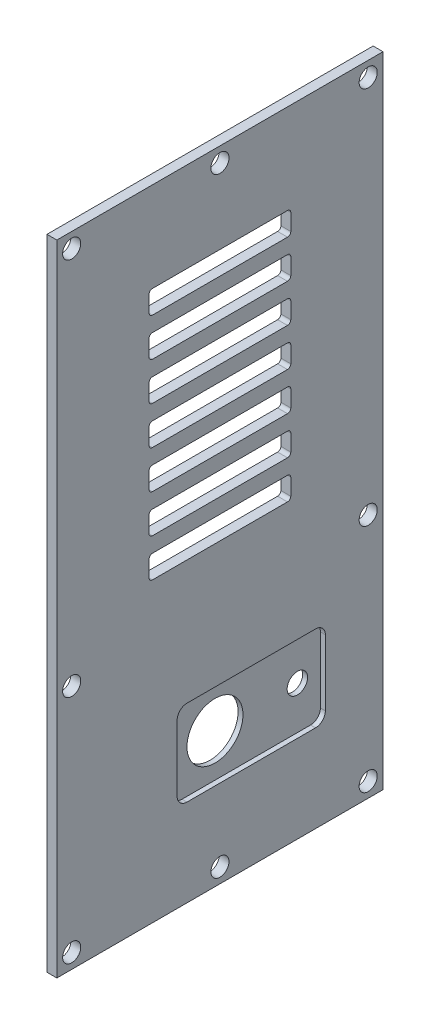
SolidWorks part; units mm, degrees
ref_plane "Front Plane" through (0, 0, 0) normal (0, 0, 1) x (1, 0, 0)
ref_plane "Top Plane" through (0, 0, 0) normal (0, 1, 0) x (1, 0, 0)
ref_plane "Right Plane" through (0, 0, 0) normal (1, 0, 0) x (0, 0, -1)
sketch "Sketch1" plane through (-74.9883, 0, 0) normal (-1, 0, 0) x (0, 0, 1)
  line L0 (-65.7307, 104.5) -> (-65.7307, -89.5)
  line L1 (-66.2307, 105) -> (33.7693, 105) construction
  line L2 (-66.2307, 105) -> (-66.2307, -90) construction
  line L3 (-66.2307, -90) -> (33.7693, -90) construction
  line L4 (33.7693, 105) -> (33.7693, -90) construction
  line L5 (-65.7307, -89.5) -> (33.2693, -89.5)
  line L6 (33.2693, 104.5) -> (33.2693, -89.5)
  line L7 (-65.7307, 104.5) -> (33.2693, 104.5)
  dimension "D1" = 0.5
extrude "Boss-Extrude1" add sketch "Sketch1" along normal blind 3
sketch "Sketch2" plane through (-77.9883, 0, 0) normal (-1, 0, 0) x (0, 0, 1)
  line L0 (-65.7307, 73.75) -> (33.2693, 73.75) construction
  line L1 (-65.7307, 104.5) -> (-65.7307, -89.5) construction
  line L2 (33.2693, -89.5) -> (33.2693, 104.5) construction
  line L3 (-16.2307, 104.5) -> (-16.2307, -89.5) construction
  line L4 (33.2693, 104.5) -> (-65.7307, 104.5) construction
  line L5 (-65.7307, -89.5) -> (33.2693, -89.5) construction
  line L6 (-65.7307, 62.15) -> (33.2693, 62.15) construction
  line L7 (33.2693, 50.55) -> (-65.7307, 50.55) construction
  line L8 (33.2693, 38.95) -> (-65.7307, 38.95) construction
  line L9 (-65.7307, 27.35) -> (33.2693, 27.35) construction
  line L10 (33.2693, 15.75) -> (-65.7307, 15.75) construction
  line L11 (33.2693, 4.15) -> (-65.7307, 4.15) construction
  line L13 (-37.7307, 70.25) -> (5.2693, 70.25)
  line L14 (-37.7307, 70.25) -> (-37.7307, 77.25)
  line L15 (-37.7307, 77.25) -> (5.2693, 77.25)
  line L16 (5.2693, 70.25) -> (5.2693, 77.25)
  line L17 (-37.7307, 70.25) -> (5.2693, 77.25) construction
  line L18 (-37.7307, 77.25) -> (5.2693, 70.25) construction
  line L19 (-37.7307, 58.65) -> (5.2693, 58.65)
  line L20 (-37.7307, 58.65) -> (-37.7307, 65.65)
  line L21 (-37.7307, 65.65) -> (5.2693, 65.65)
  line L22 (5.2693, 58.65) -> (5.2693, 65.65)
  line L23 (-37.7307, 58.65) -> (5.2693, 65.65) construction
  line L24 (-37.7307, 65.65) -> (5.2693, 58.65) construction
  line L25 (-37.7307, 47.05) -> (5.2693, 47.05)
  line L26 (-37.7307, 47.05) -> (-37.7307, 54.05)
  line L27 (-37.7307, 54.05) -> (5.2693, 54.05)
  line L28 (5.2693, 47.05) -> (5.2693, 54.05)
  line L29 (-37.7307, 47.05) -> (5.2693, 54.05) construction
  line L30 (-37.7307, 54.05) -> (5.2693, 47.05) construction
  line L31 (-37.7307, 35.45) -> (5.2693, 35.45)
  line L32 (-37.7307, 35.45) -> (-37.7307, 42.45)
  line L33 (-37.7307, 42.45) -> (5.2693, 42.45)
  line L34 (5.2693, 35.45) -> (5.2693, 42.45)
  line L35 (-37.7307, 35.45) -> (5.2693, 42.45) construction
  line L36 (-37.7307, 42.45) -> (5.2693, 35.45) construction
  line L37 (-37.7307, 23.85) -> (5.2693, 23.85)
  line L38 (-37.7307, 23.85) -> (-37.7307, 30.85)
  line L39 (-37.7307, 30.85) -> (5.2693, 30.85)
  line L40 (5.2693, 23.85) -> (5.2693, 30.85)
  line L41 (-37.7307, 23.85) -> (5.2693, 30.85) construction
  line L42 (-37.7307, 30.85) -> (5.2693, 23.85) construction
  line L43 (-37.7307, 12.25) -> (5.2693, 12.25)
  line L44 (-37.7307, 12.25) -> (-37.7307, 19.25)
  line L45 (-37.7307, 19.25) -> (5.2693, 19.25)
  line L46 (5.2693, 12.25) -> (5.2693, 19.25)
  line L47 (-37.7307, 12.25) -> (5.2693, 19.25) construction
  line L48 (-37.7307, 19.25) -> (5.2693, 12.25) construction
  line L49 (-37.7307, 0.65) -> (5.2693, 0.65)
  line L50 (-37.7307, 0.65) -> (-37.7307, 7.65)
  line L51 (-37.7307, 7.65) -> (5.2693, 7.65)
  line L52 (5.2693, 0.65) -> (5.2693, 7.65)
  line L53 (-37.7307, 0.65) -> (5.2693, 7.65) construction
  line L54 (-37.7307, 7.65) -> (5.2693, 0.65) construction
  point P24 (-16.2307, 73.75)
  point P25 (-16.2307, 62.15)
  point P26 (-16.2307, 50.55)
  point P27 (-16.2307, 38.95)
  point P28 (-16.2307, 27.35)
  point P29 (-16.2307, 15.75)
  point P30 (-16.2307, 4.15)
  point P31 (-16.2307, 73.75)
  point P36 (-16.2307, 62.15)
  point P41 (-16.2307, 50.55)
  point P46 (-16.2307, 38.95)
  point P51 (-16.2307, 27.35)
  point P56 (-16.2307, 15.75)
  point P61 (-16.2307, 4.15)
  dimension "D1" = 43
  dimension "D2" = 7
extrude "Cut-Extrude1" cut sketch "Sketch2" against normal through all
fillet "Fillet1" radius 1 28 edges at (-76.4883, 7.65, 5.2693) (-76.4883, 0.65, 5.2693) (-76.4883, 0.65, -37.7307) (-76.4883, 7.65, -37.7307) (-76.4883, 12.25, -37.7307) (-76.4883, 19.25, -37.7307) (-76.4883, 12.25, 5.2693) (-76.4883, 19.25, 5.2693) (-76.4883, 23.85, 5.2693) (-76.4883, 23.85, -37.7307) (-76.4883, 30.85, -37.7307) (-76.4883, 30.85, 5.2693) (-76.4883, 42.45, 5.2693) (-76.4883, 35.45, 5.2693) (-76.4883, 35.45, -37.7307) (-76.4883, 42.45, -37.7307) (-76.4883, 47.05, -37.7307) (-76.4883, 54.05, -37.7307) (-76.4883, 47.05, 5.2693) (-76.4883, 54.05, 5.2693) (-76.4883, 58.65, 5.2693) (-76.4883, 65.65, 5.2693) (-76.4883, 65.65, -37.7307) (-76.4883, 58.65, -37.7307) (-76.4883, 70.25, -37.7307) (-76.4883, 77.25, -37.7307) (-76.4883, 70.25, 5.2693) (-76.4883, 77.25, 5.2693)
sketch "Sketch3" plane through (-77.9883, 0, 0) normal (-1, 0, 0) x (0, 0, 1)
  line L0 (23.7693, -80) -> (-56.2307, -80) construction
  line L5 (-56.2307, -90) -> (-56.2307, 105) construction
  line L6 (33.2693, -89.5) -> (33.2693, 104.5) construction
  circle A0 centre (-16.2307, -50) radius 8.5
  circle A1 centre (-41.2307, -50) radius 3.1
  dimension "D3" = 6.2
  dimension "D4" = 17
  dimension "D1" = 30
  dimension "D2" = 30
  dimension "D5" = 49.5
  dimension "D6" = 15
extrude "Cut-Extrude2" cut sketch "Sketch3" against normal through all
sketch "Sketch4" plane through (-74.9883, 0, 0) normal (1, 0, 0) x (0, 0, -1)
  line L1 (3.2307, -63) -> (48.2307, -63)
  line L2 (3.2307, -63) -> (3.2307, -37)
  line L3 (3.2307, -37) -> (48.2307, -37)
  line L4 (48.2307, -63) -> (48.2307, -37)
  line L5 (3.2307, -63) -> (48.2307, -37) construction
  line L6 (3.2307, -37) -> (48.2307, -63) construction
  circle A0 centre (16.2307, -50) radius 8.5 construction
  point P0 (25.7307, -50)
  dimension "D1" = 45
  dimension "D2" = 26
  dimension "D3" = 0
  dimension "D4" = 13
extrude "Cut-Extrude3" cut sketch "Sketch4" against normal blind 1.5
fillet "Fillet2" radius 3 4 edges at (-75.7383, -63, -48.2307) (-75.7383, -37, -48.2307) (-75.7383, -63, -3.2307) (-75.7383, -37, -3.2307)
sketch "Sketch5" plane through (-77.9883, 0, 0) normal (-1, 0, 0) x (0, 0, 1)
  line L0 (-65.7307, 104.5) -> (-65.7307, -89.5) construction
  line L1 (33.2693, 104.5) -> (-65.7307, 104.5) construction
  line L2 (-65.7307, -89.5) -> (33.2693, -89.5) construction
  line L3 (33.2693, -89.5) -> (33.2693, 104.5) construction
  circle A0 centre (-61.2307, 100) radius 2.75
  circle A1 centre (28.7693, 100) radius 2.75
  circle A2 centre (-61.2307, -15) radius 2.75
  circle A3 centre (-61.2307, -85) radius 2.75
  circle A4 centre (28.7693, -85) radius 2.75
  circle A5 centre (28.7693, -15) radius 2.75
  circle A6 centre (-16.2307, 100) radius 2.75
  circle A7 centre (-16.2307, -85) radius 2.75
  dimension "D1" = 5.5
  dimension "D7" = 45
  dimension "D8" = 5.5
  dimension "D9" = 5.5
  dimension "D2" = 4.5
  dimension "D3" = 4.5
  dimension "D4" = 4.5
  dimension "D5" = 4.5
  dimension "D6" = 70
extrude "Cut-Extrude4" cut sketch "Sketch5" against normal through all
